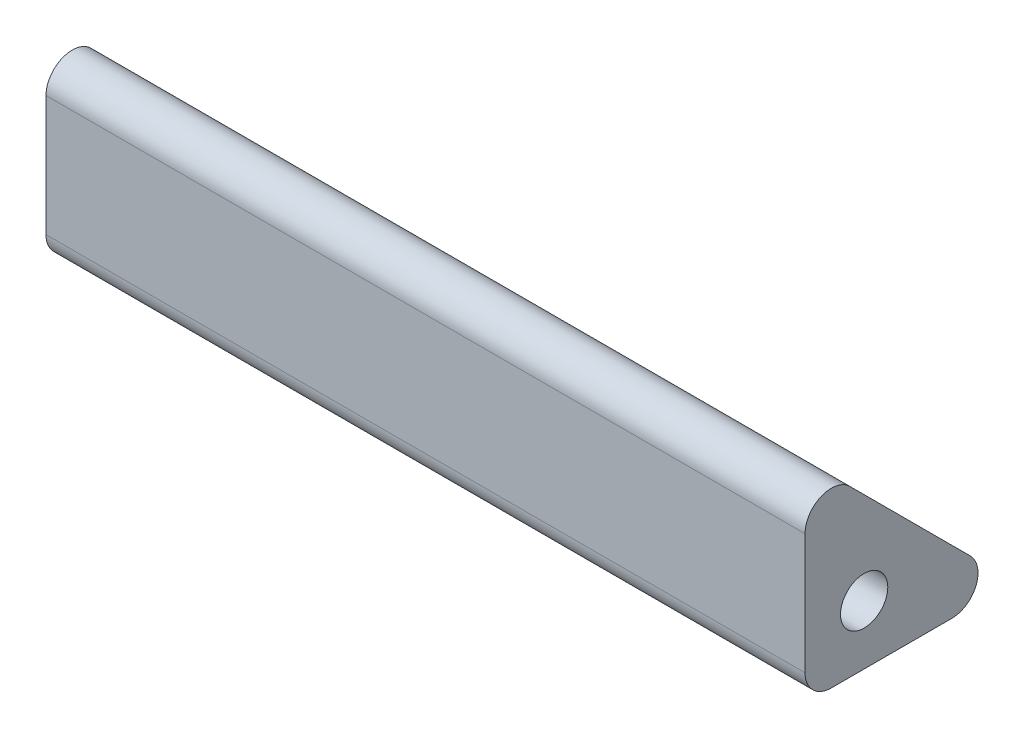
SolidWorks part; units mm, degrees
ref_plane "Front Plane" through (0, 0, 0) normal (0, 0, 1) x (1, 0, 0)
ref_plane "Top Plane" through (0, 0, 0) normal (0, 1, 0) x (1, 0, 0)
ref_plane "Right Plane" through (0, 0, 0) normal (1, 0, 0) x (0, 0, -1)
sketch "Sketch1" plane through (0, 0, 0) normal (1, 0, 0) x (0, 0, -1)
  line L0 (-2.25, 5.75) -> (-2.25, -2.25)
  line L1 (-2.25, -2.25) -> (5.75, -2.25)
  line L3 (-2.25, 5.75) -> (5.75, -2.25)
  circle A0 centre (0, 0) radius 0.9
  dimension "D1" = 1.8
  dimension "D2" = 8
  dimension "D3" = 8
  dimension "D4" = 2.25
  dimension "D5" = 2.25
extrude "Boss-Extrude1" add sketch "Sketch1" along normal blind 28.9
fillet "Fillet1" radius 1 3 edges at (14.45, -2.25, 2.25) (14.45, -2.25, -5.75) (14.45, 5.75, 2.25)
